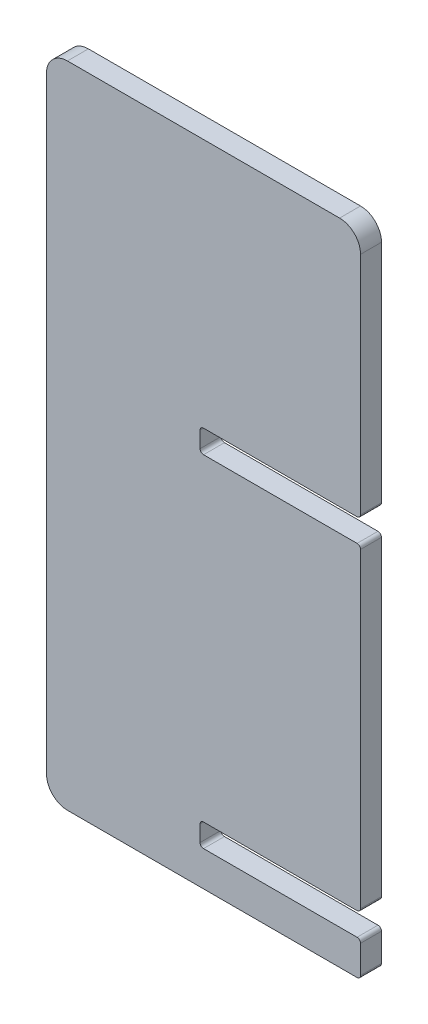
SolidWorks part; units mm, degrees
ref_plane "Alzado" through (0, 0, 0) normal (0, 0, 1) x (1, 0, 0)
ref_plane "Planta" through (0, 0, 0) normal (0, 1, 0) x (1, 0, 0)
ref_plane "Vista lateral" through (0, 0, 0) normal (1, 0, 0) x (0, 0, -1)
sketch "Croquis1" plane through (0, 0, 0) normal (0, 0, 1) x (1, 0, 0)
  line L1 (-22.5, 45) -> (22.5, 45)
  line L2 (-22.5, 45) -> (-22.5, -48)
  line L3 (-22.5, -48) -> (22.5, -48)
  line L4 (22.5, 45) -> (22.5, -48)
  dimension "D1" = 45
  dimension "D2" = 22.5
  dimension "D3" = 93
  dimension "D4" = 45
extrude "Saliente-Extruir1" add sketch "Croquis1" along normal blind 3 contours L2 L3 L4 L1
sketch "Croquis2" plane through (0, 0, 3) normal (0, 0, 1) x (1, 0, 0)
  line L0 (22.5, 45) -> (22.5, -48) construction
  line L1 (22.5, 9.1795) -> (-0.5, 9.1795)
  line L2 (22.5, 9.1795) -> (22.5, 5.8795)
  line L3 (22.5, 5.8795) -> (-0.5, 5.8795)
  line L4 (-0.5, 9.1795) -> (-0.5, 5.8795)
  dimension "D1" = 23
  dimension "D2" = 3.3
  dimension "D3" = 5.8795
extrude "Cortar-Extruir1" cut sketch "Croquis2" against normal up to surface (3 mm away) up to face at (0, -1.5, 0)
sketch "Croquis3" plane through (0, 0, 3) normal (0, 0, 1) x (1, 0, 0)
  line L0 (22.5, 5.8795) -> (22.5, -48) construction
  line L1 (22.5, -39.7) -> (-0.5, -39.7)
  line L2 (22.5, -39.7) -> (22.5, -43)
  line L3 (22.5, -43) -> (-0.5, -43)
  line L4 (-0.5, -39.7) -> (-0.5, -43)
  line L5 (-22.5, -48) -> (22.5, -48) construction
  dimension "D1" = 3.3
  dimension "D2" = 5
  dimension "D3" = 23
extrude "Cortar-Extruir2" cut sketch "Croquis3" against normal up to surface (3 mm away) up to face at (5.5, 3.0147, 0)
fillet "Redondeo1" radius 3 3 edges at (-22.5, -48, 1.5) (22.5, 45, 1.5) (-22.5, 45, 1.5)
fillet "Redondeo2" radius 0.5 9 edges at (22.5, 5.8795, 1.5) (22.5, 9.1795, 1.5) (-0.5, 9.1795, 1.5) (-0.5, 5.8795, 1.5) (22.5, -43, 1.5) (-0.5, -43, 1.5) (-0.5, -39.7, 1.5) (22.5, -39.7, 1.5) (22.5, -48, 1.5)
